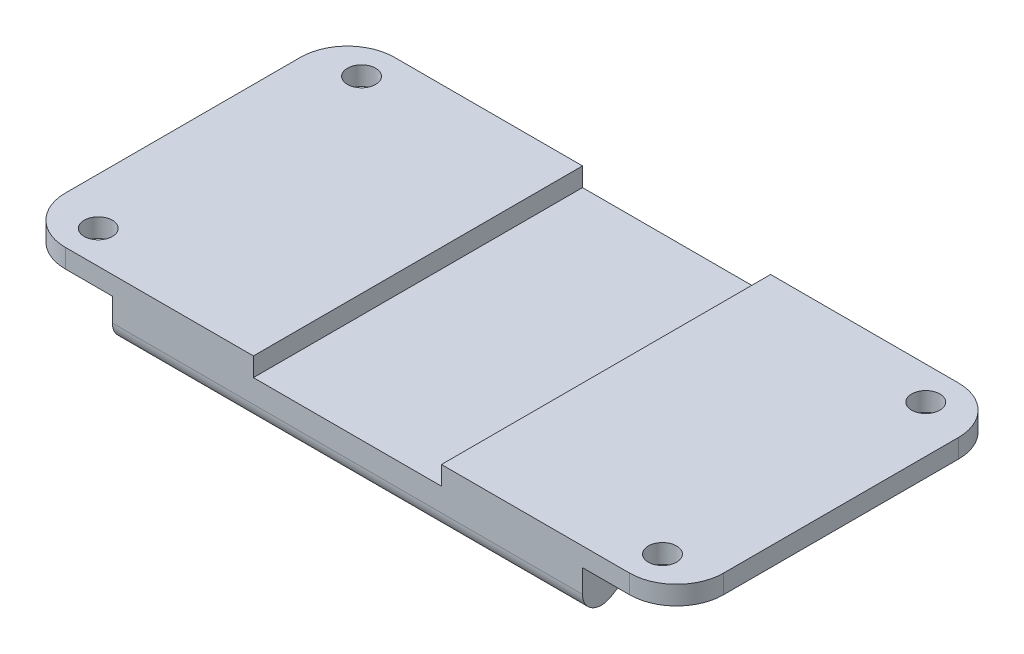
SolidWorks part; units mm, degrees
material "PEI"
ref_plane "Front Plane" through (0, 0, 0) normal (0, 0, 1) x (1, 0, 0)
ref_plane "Top Plane" through (0, 0, 0) normal (0, 1, 0) x (1, 0, 0)
ref_plane "Right Plane" through (0, 0, 0) normal (1, 0, 0) x (0, 0, -1)
sketch "Sketch1" plane through (0, 0, 0) normal (0, 1, 0) x (1, 0, 0)
  line L1 (25, -17.5) -> (-25, -17.5)
  line L2 (25, -17.5) -> (25, 17.5)
  line L3 (25, 17.5) -> (-25, 17.5)
  line L4 (-25, -17.5) -> (-25, 17.5)
  line L5 (25, -17.5) -> (-25, 17.5) construction
  line L6 (25, 17.5) -> (-25, -17.5) construction
  point P0 (0, 0)
  dimension "D1" = 35
  dimension "D2" = 50
extrude "Boss-Extrude1" add sketch "Sketch1" against normal blind 8
sketch "Sketch2" plane through (25, 0, 0) normal (1, 0, 0) x (0, 0, -1)
  line L0 (-17.5, -8) -> (-12.5, -5)
  line L1 (-12.5, -5) -> (12.5, -5)
  line L2 (0, -5) -> (0, -8)
  line L3 (17.5, -8) -> (12.5, -5)
  line L4 (17.5, 0) -> (-17.5, 0)
  line L5 (-17.5, 0) -> (-17.5, -8)
  line L6 (-17.5, -8) -> (17.5, -8)
  line L7 (17.5, -8) -> (17.5, 0)
  line L8 (17.5, 0) -> (-17.5, 0)
  line L9 (-17.5, 0) -> (-17.5, -8)
  line L10 (-17.5, -8) -> (17.5, -8)
  line L11 (17.5, -8) -> (17.5, 0)
  line M7 (-17.5, -8) -> (17.5, -8)
  dimension "D2" = 5
  dimension "D3" = 3
  dimension "D1" = 0
extrude "Cut-Extrude1" cut sketch "Sketch2" against normal through all and the other way through all contours L2 L1 L0 M7 | L3 L1 L2 M7 region at (25, -6.5833, 7.5694) region at (25, -6.5833, -7.5694)
fillet "Fillet1" radius 2 4 edges at (0, -5, 12.5) (0, -5, -12.5) (0, -8, -17.5) (0, -8, 17.5)
sketch "Sketch3" plane through (0, 0, 17.5) normal (0, 0, 1) x (1, 0, 0)
  line L0 (-25, 0) -> (25, 0) construction
  line L1 (-10, 2) -> (10, 2)
  line L2 (-10, 2) -> (-10, -2)
  line L3 (-10, -2) -> (10, -2)
  line L4 (-25, 0) -> (-25, -4.4676)
  line L5 (-25, -4.4676) -> (25, -4.4676)
  line L6 (25, -4.4676) -> (25, 0)
  line L7 (25, 0) -> (-25, 0)
  line L8 (-25, 0) -> (-25, -4.4676)
  line L9 (-25, -4.4676) -> (25, -4.4676)
  line L10 (25, -4.4676) -> (25, 0)
  line L11 (25, 0) -> (-25, 0)
  line L12 (10, 2) -> (10, -2)
  line L13 (-10, 2) -> (10, -2) construction
  line L14 (-10, -2) -> (10, 2) construction
  line L15 (0, 0) -> (0, -4.4676)
  point P2 (0, 0)
  point P9 (0, 0)
  point P18 (0, 0)
  line M10 (25, 0) -> (-25, 0)
  dimension "D2" = 20
  dimension "D3" = 4
  dimension "D1" = 0
sketch "Sketch5" plane through (-25, 0, 0) normal (-1, 0, 0) x (0, 0, 1)
  line L1 (-17.5, 0) -> (17.5, 0)
  line L2 (-17.5, 0) -> (-17.5, -2)
  line L3 (-17.5, -2) -> (17.5, -2)
  line L4 (17.5, 0) -> (17.5, -2)
  line L6 (-17.5, 0) -> (-17.5, -4.4676)
  line L7 (-14.471, -6.1826) -> (-12.975, -5.285)
  line L8 (-11.946, -5) -> (11.946, -5)
  line L9 (12.975, -5.285) -> (14.471, -6.1826)
  line L10 (17.5, -4.4676) -> (17.5, 0)
  line L11 (17.5, 0) -> (-17.5, 0)
  line L12 (-17.5, 0) -> (-17.5, -4.4676)
  line L13 (-14.471, -6.1826) -> (-12.975, -5.285)
  line L14 (-11.946, -5) -> (11.946, -5)
  line L15 (12.975, -5.285) -> (14.471, -6.1826)
  line L16 (17.5, -4.4676) -> (17.5, 0)
  line L17 (17.5, 0) -> (-17.5, 0)
  arc A4 (-17.5, -4.4676) -> (-14.471, -6.1826) centre (-15.5, -4.4676) ccw
  arc A5 (-11.946, -5) -> (-12.975, -5.285) centre (-11.946, -7) ccw
  arc A6 (12.975, -5.285) -> (11.946, -5) centre (11.946, -7) ccw
  arc A7 (14.471, -6.1826) -> (17.5, -4.4676) centre (15.5, -4.4676) ccw
  arc A8 (-17.5, -4.4676) -> (-14.471, -6.1826) centre (-15.5, -4.4676) ccw
  arc A9 (-11.946, -5) -> (-12.975, -5.285) centre (-11.946, -7) ccw
  arc A10 (12.975, -5.285) -> (11.946, -5) centre (11.946, -7) ccw
  arc A11 (14.471, -6.1826) -> (17.5, -4.4676) centre (15.5, -4.4676) ccw
  line M13 (-17.5, 0) -> (-17.5, -4.4676)
  line M21 (17.5, -4.4676) -> (17.5, 0)
  line M22 (17.5, 0) -> (-17.5, 0)
  dimension "D2" = 2
  dimension "D1" = 0
extrude "Boss-Extrude2" add sketch "Sketch5" along normal blind 10 contours L3 M13 M21 M22 region at (-25, -1, 0)
mirror "Mirror1" about plane through (0, 0, 0) normal (1, 0, 0) of "Boss-Extrude2"
sketch "Sketch6" plane through (0, 0, 0) normal (0, 1, 0) x (1, 0, 0)
  line L0 (0, 0) -> (-30, 0)
  line L1 (-30, 0) -> (-30, 14)
  line L2 (0, 0) -> (0, 17.5)
  line L4 (35, 17.5) -> (-35, 17.5)
  line L5 (-35, 17.5) -> (-35, -17.5)
  line L6 (-35, -17.5) -> (35, -17.5)
  line L7 (35, -17.5) -> (35, 17.5)
  line L8 (35, 17.5) -> (-35, 17.5)
  line L9 (-35, 17.5) -> (-35, -17.5)
  line L10 (-35, -17.5) -> (35, -17.5)
  line L11 (35, -17.5) -> (35, 17.5)
  circle A0 centre (-30, 14) radius 1.5
  circle A1 centre (-30, -14) radius 1.5
  circle A2 centre (30, -14) radius 1.5
  circle A3 centre (30, 14) radius 1.5
  dimension "D4" = 3
  dimension "D2" = 14
  dimension "D3" = 30
  dimension "D1" = 0
extrude "Cut-Extrude2" cut sketch "Sketch6" against normal blind 10 contours A0 | A1 | A3 | A2 region at (-31.0307, 0, -15.0307) region at (-30, 0, 14) region at (30, 0, 14) region at (30, 0, -14)
extrude "Cut-Extrude3" cut sketch "Sketch3" against normal through all contours L11 L15 L3 L12 | L15 L2 L3 M10 region at (-5, -1, 17.5) region at (5, -1, 17.5)
fillet "Fillet3" radius 5 4 edges at (35, -1, 17.5) (35, -1, -17.5) (-35, -1, -17.5) (-35, -1, 17.5)
